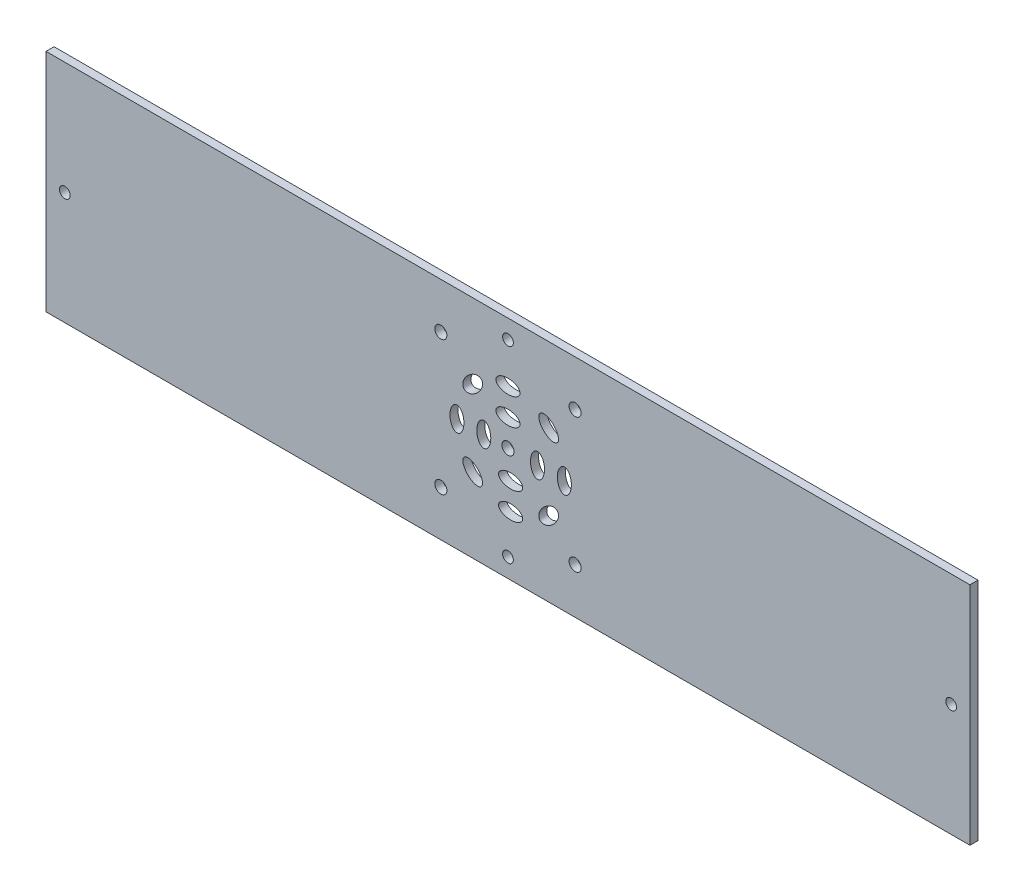
SolidWorks part; units mm, degrees
material "PMMA"
ref_plane "Piano frontale" through (0, 0, 0) normal (0, 0, 1) x (1, 0, 0)
ref_plane "Piano superiore" through (0, 0, 0) normal (0, 1, 0) x (1, 0, 0)
ref_plane "Piano destro" through (0, 0, 0) normal (1, 0, 0) x (0, 0, -1)
sketch "Schizzo1" plane through (0, 0, 0) normal (0, 0, 1) x (1, 0, 0)
  line L0 (0, 0) -> (0, 84)
  line L1 (0, 84) -> (344, 84)
  line L2 (344, 84) -> (344, 0)
  line L3 (344, 0) -> (0, 0)
  line L4 (0, 42) -> (344, 42) construction
  line L5 (172, 42) -> (172, 123.488) construction
  circle A0 centre (7, 42) radius 2
  circle A1 centre (172, 77) radius 2
  circle A2 centre (172, 7) radius 2
  circle A3 centre (337, 42) radius 2
  circle A4 centre (172, 42) radius 2.25
  circle A5 centre (147, 67) radius 2.25
  circle A6 centre (147, 17) radius 2.25
  circle A7 centre (197, 17) radius 2.25
  circle A8 centre (197, 67) radius 2.25
  ellipse E0 centre (172, 52) end of major axis (167.5, 52) minor radius 2.6
  ellipse E1 centre (183, 42) end of major axis (183, 37.5) minor radius 2.6
  ellipse E2 centre (173, 32) end of major axis (168.5, 32) minor radius 2.6
  ellipse E3 centre (163, 42) end of major axis (163, 46.5) minor radius 2.6
  ellipse E4 centre (172, 62) end of major axis (167.5, 62) minor radius 2.6
  ellipse E5 centre (187.1421, 56.1421) end of major axis (190.3241, 52.9602) minor radius 2.6
  ellipse E6 centre (193, 42) end of major axis (193, 37.5) minor radius 2.6
  ellipse E7 centre (187.1421, 27.8579) end of major axis (183.9602, 24.6759) minor radius 2.6
  ellipse E8 centre (173, 22) end of major axis (168.5, 22) minor radius 2.6
  ellipse E9 centre (158.8579, 27.8579) end of major axis (155.6759, 31.0398) minor radius 2.6
  ellipse E10 centre (153, 42) end of major axis (153, 46.5) minor radius 2.6
  ellipse E11 centre (158.8579, 56.1421) end of major axis (162.0398, 59.3241) minor radius 2.6
  point P46 (173, 42)
  point P94 (173, 42)
  dimension "D3" = 7
  dimension "D4" = 7
  dimension "D6" = 4
  dimension "D5" = 4.5
  dimension "D1" = 84
  dimension "D2" = 344
  dimension "D7" = 10
  dimension "D8" = 9
  dimension "D9" = 5.2
  dimension "D10" = 10
  dimension "D11" = 9
  dimension "D12" = 5.2
  dimension "D13" = 50
  dimension "D14" = 50
extrude "Estrusione-Estrusione1" add sketch "Schizzo1" along normal blind 3
